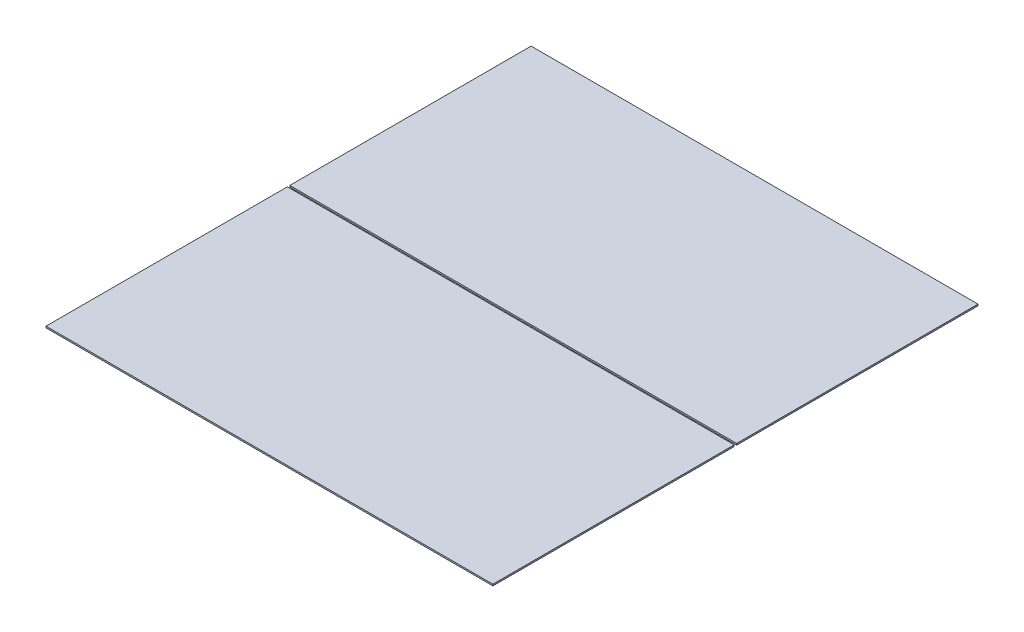
SolidWorks part; units mm, degrees
ref_plane "Front Plane" through (0, 0, 0) normal (0, 0, 1) x (1, 0, 0)
ref_plane "Top Plane" through (0, 0, 0) normal (0, 1, 0) x (1, 0, 0)
ref_plane "Right Plane" through (0, 0, 0) normal (1, 0, 0) x (0, 0, -1)
sketch "Sketch1" plane through (0, 0, 0) normal (0, 1, 0) x (1, 0, 0)
  line L1 (-736.6, 10) -> (736.6, 10)
  line L2 (-736.6, 10) -> (-736.6, 800.1)
  line L3 (-736.6, 800.1) -> (736.6, 800.1)
  line L4 (736.6, 10) -> (736.6, 800.1)
  line L5 (-736.6, 10) -> (736.6, 800.1) construction
  line L6 (-736.6, 800.1) -> (736.6, 10) construction
  line L11 (-736.6, -800.1) -> (736.6, -800.1)
  line L12 (-736.6, -800.1) -> (-736.6, -10)
  line L13 (-736.6, -10) -> (736.6, -10)
  line L14 (736.6, -800.1) -> (736.6, -10)
  point P0 (0, 0)
extrude "Boss-Extrude1" add sketch "Sketch1" along normal blind 2.5 and the other way blind 2.5
sketch "Sketch2" plane through (0, 0, 0) normal (0, 1, 0) x (1, 0, 0)
  line L5 (-736.6, 800.1) -> (736.6, 800.1)
  line L6 (-736.6, 800.1) -> (-736.6, 10)
  line L11 (-736.6, 10) -> (736.6, 10)
  line L12 (736.6, 800.1) -> (736.6, 10)
  line L13 (-736.6, -10) -> (736.6, -10)
  line L14 (-736.6, -10) -> (-736.6, -800.1)
  line L15 (-736.6, -800.1) -> (736.6, -800.1)
  line L16 (736.6, -10) -> (736.6, -800.1)
  line L17 (-742.6, 806.1) -> (742.6, 806.1)
  line L18 (-742.6, 806.1) -> (-742.6, 4)
  line L19 (-742.6, 4) -> (742.6, 4)
  line L20 (742.6, 806.1) -> (742.6, 4)
  line L21 (742.6, -806.1) -> (-742.6, -806.1)
  line L22 (742.6, -806.1) -> (742.6, -4)
  line L23 (742.6, -4) -> (-742.6, -4)
  line L24 (-742.6, -806.1) -> (-742.6, -4)
  dimension "D1" = 6
  dimension "D2" = 6
  dimension "D3" = 6
  dimension "D4" = 6
  dimension "D5" = 6
  dimension "D6" = 6
extrude "Boss-Extrude2" add sketch "Sketch2" along normal up to surface and the other way up to surface up to face at (0, 2.5, -405.05) other way up to face at (0, -2.5, -405.05)
